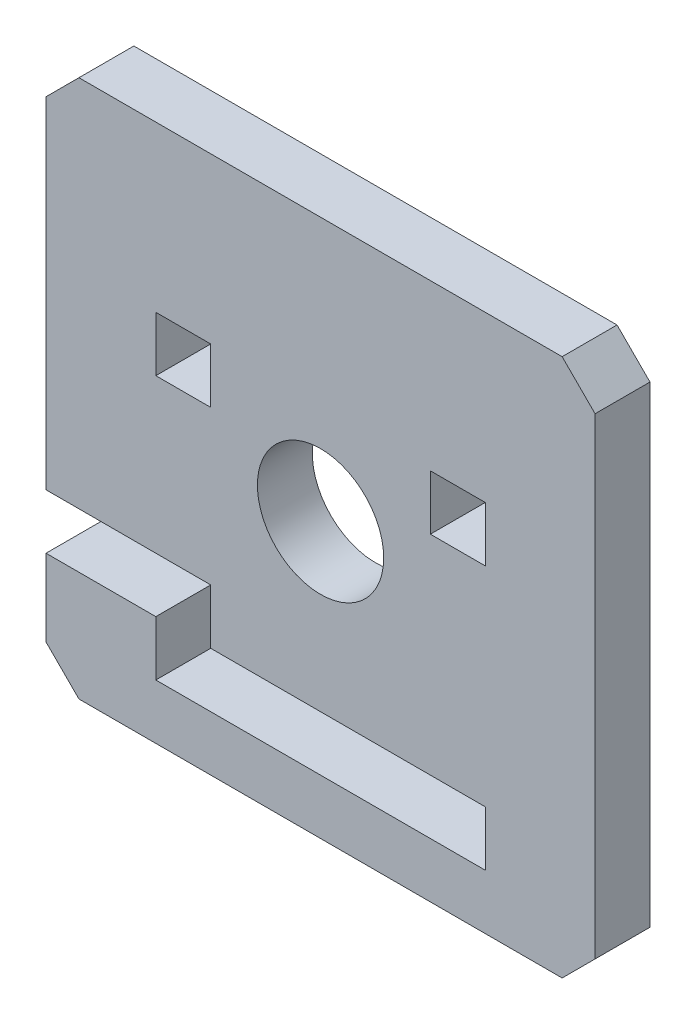
SolidWorks part; units mm, degrees
material "6061-T4 (SS)"
ref_plane "Front Plane" through (0, 0, 0) normal (0, 0, 1) x (1, 0, 0)
ref_plane "Top Plane" through (0, 0, 0) normal (0, 1, 0) x (1, 0, 0)
ref_plane "Right Plane" through (0, 0, 0) normal (1, 0, 0) x (0, 0, -1)
sketch "Sketch1" plane through (0, 0, 0) normal (0, 0, 1) x (1, 0, 0)
  line L0 (-25, 21) -> (-22, 24)
  line L1 (-22, 24) -> (22, 24)
  line L2 (22, 24) -> (25, 21)
  line L3 (25, 21) -> (25, -22)
  line L4 (25, -22) -> (22, -25)
  line L5 (22, -25) -> (-22, -25)
  line L6 (-22, -25) -> (-25, -22)
  line L7 (-25, -22) -> (-25, -15)
  line L8 (-25, -15) -> (-15, -15)
  line L9 (-15, -15) -> (-15, -20)
  line L10 (-15, -20) -> (15, -20)
  line L11 (15, -20) -> (15, -15)
  line L12 (15, -15) -> (-10, -15)
  line L13 (-10, -15) -> (-10, -10)
  line L14 (-10, -10) -> (-25, -10)
  line L15 (-25, -10) -> (-25, 21)
  line L16 (0, 0) -> (0, 30.1749) construction
  line L21 (-10, 4) -> (-15, 9) construction
  line L22 (-10, 9) -> (-15, 4) construction
  line L23 (10, 9) -> (15, 9)
  line L24 (10, 9) -> (10, 4)
  line L25 (10, 4) -> (15, 4)
  line L26 (15, 9) -> (15, 4)
  line L27 (10, 9) -> (15, 4) construction
  line L28 (10, 4) -> (15, 9) construction
  line L29 (-15, 9) -> (-15, 4)
  line L30 (-10, 4) -> (-15, 4)
  line L31 (-10, 9) -> (-10, 4)
  line L32 (-10, 9) -> (-15, 9)
  circle A0 centre (0, 0) radius 5.75
  point P5 (-12.5, 6.5)
  point P28 (12.5, 6.5)
  point P29 (0, 24)
  point P67 (0, -25)
  dimension "D1" = 11.5
  dimension "D2" = 50
  dimension "D3" = 44
  dimension "D4" = 30
  dimension "D5" = 25
  dimension "D6" = 45
  dimension "D7" = 15
  dimension "D8" = 31
  dimension "D9" = 7
  dimension "D10" = 5
  dimension "D11" = 49
  dimension "D12" = 24
  dimension "D13" = 43
  dimension "D14" = 45
  dimension "D15" = 5
  dimension "D16" = 5
  dimension "D17" = 15
  dimension "D18" = 10
extrude "Boss-Extrude1" add sketch "Sketch1" along normal blind 5
